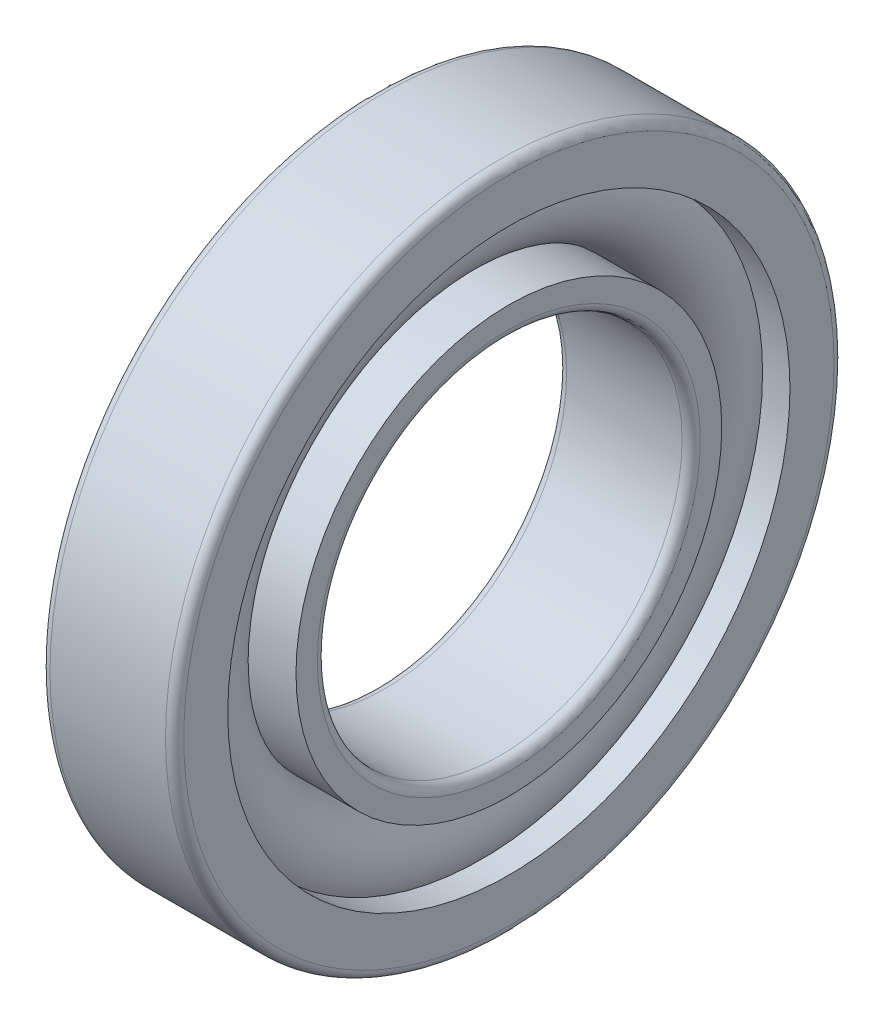
SolidWorks part; units mm, degrees
ref_plane "Plane1" through (0, 0, 0) normal (0, 0, 1) x (1, 0, 0)
ref_plane "Plane2" through (0, 0, 0) normal (0, 1, 0) x (1, 0, 0)
ref_plane "Plane3" through (0, 0, 0) normal (1, 0, 0) x (0, 0, -1)
sketch "Clipboard" plane through (0, 0, 0) normal (0, 0, 1) x (1, 0, 0)
  line L0 (-10, 0) -> (10, 0) construction
  line L1 (0, 0) -> (22.3471, -0.7804)
  line L2 (0, 0) -> (42.4741, 1.4832)
  line L3 (0, 0) -> (22.3471, -0.7804)
  line L4 (0, 0) -> (-22.3573, -0.3902)
  dimension "BallCLRad" = 42.5
sketch "CagSpiSke" plane through (0, 0, 0) normal (0, 0, 1) x (1, 0, 0)
  line L0 (1.875, 41.25) -> (1.875, 43.75)
  line L1 (1.875, 43.75) -> (-1.875, 43.75)
  line L2 (-1.875, 43.75) -> (-1.875, 41.25)
  line L3 (-1.875, 41.25) -> (1.875, 41.25)
  line L4 (-20.6375, 0) -> (20.6375, 0) construction
  line L5 (0, 0) -> (0, 23.7692) construction
  dimension "OD" = 87.5
  dimension "ID" = 82.5
revolve "CageSpine" add sketch "CagSpiSke" angle 0.001 about L4
ref_axis "Axis1" through (-50, 0, 0) along (1, 0, 0)
sketch "CagBalSke" plane through (0, 0, 0) normal (0, 0, 1) x (1, 0, 0)
  line L0 (-8.25, 42.5) -> (8.25, 42.5)
  line L1 (-1.905, 42.5) -> (1.905, 42.5) construction
  line L2 (-10, 0) -> (10, 0) construction
  line L3 (0, 0) -> (0, 24) construction
  arc A0 (8.25, 42.5) -> (-8.25, 42.5) centre (0, 42.5) cw
  dimension "BallCLRad" = 42.5
revolve "CageBall" [suppressed] add sketch "CagBalSke" angle 360 about L1 reverse direction yes
pattern_circular "CageBalls" [suppressed] count 2 every 180 about axis through (-50, 0, 0) along (1, 0, 0)
sketch "CagTrmODSke" plane through (0, 0, 0) normal (0, 0, 1) x (1, 0, 0)
  line L0 (8.251, 43.75) -> (8.251, 50.751)
  line L1 (8.251, 50.751) -> (-8.251, 50.751)
  line L2 (-8.251, 50.751) -> (-8.251, 43.75)
  line L3 (-8.251, 43.75) -> (8.251, 43.75)
  line L4 (-20.6375, 0) -> (20.6375, 0) construction
  line L5 (0, 0) -> (0, 25) construction
  dimension "Width" = 16.502
  dimension "ID" = 87.5
  dimension "OD" = 101.502
revolve "CageTrimOD" [suppressed] cut sketch "CagTrmODSke" angle 360 about L4 reverse direction yes
sketch "CagTrmIDSke" plane through (0, 0, 0) normal (0, 0, 1) x (1, 0, 0)
  line L0 (8.251, 34.251) -> (8.251, 41.25)
  line L1 (8.251, 41.25) -> (-8.251, 41.25)
  line L2 (-8.251, 41.25) -> (-8.251, 34.251)
  line L3 (-8.251, 34.251) -> (8.251, 34.251)
  line L4 (-20.6375, 0) -> (20.6375, 0) construction
  line L5 (0, 0) -> (0, 25) construction
  dimension "Width" = 16.502
  dimension "ID" = 68.502
  dimension "OD" = 82.5
revolve "CageTrimID" [suppressed] cut sketch "CagTrmIDSke" angle 360 about L4 reverse direction yes
sketch "BalSimSke" plane through (0, 0, 0) normal (0, 0, 1) x (1, 0, 0)
  line L0 (-10, 0) -> (10, 0) construction
  line L1 (-10, 42.5) -> (10, 42.5) construction
  line L2 (0, 0) -> (0, 23) construction
  circle A0 centre (0, 42.5) radius 7.5
  dimension "BallCLRad" = 42.5
  dimension "Ball_diameter" = 15
revolve "BallsSimplified" add sketch "BalSimSke" angle 360 about L0
sketch "BalDetSke" plane through (0, 0, 0) normal (0, 0, 1) x (1, 0, 0)
  line L0 (-7.5, 42.5) -> (7.5, 42.5)
  line L1 (-1.905, 42.5) -> (1.905, 42.5) construction
  line L2 (0, 0) -> (0, 25) construction
  arc A0 (7.5, 42.5) -> (-7.5, 42.5) centre (0, 42.5) cw
  dimension "BallCLRad" = 42.5
  dimension "Ball_diameter" = 15
revolve "BallDetailed" [suppressed] add sketch "BalDetSke" angle 360 about L1 reverse direction yes
sketch "InnRacSke" plane through (0, 0, 0) normal (0, 0, 1) x (1, 0, 0)
  line L0 (-6.4663, 38.75) -> (-11, 38.75)
  line L1 (-11, 38.75) -> (-11, 31.5)
  line L2 (-9.5, 30) -> (9.5, 30)
  line L3 (11, 31.5) -> (11, 35.025)
  line L4 (0, 35.025) -> (11, 35.025)
  line L5 (-20.6375, 0) -> (20.6375, 0) construction
  line L6 (0, 0) -> (0, 30) construction
  arc A0 (-11, 31.5) -> (-9.5, 30) centre (-9.5, 31.5) ccw
  arc A1 (9.5, 30) -> (11, 31.5) centre (9.5, 31.5) ccw
  arc A2 (0, 35.025) -> (-6.4663, 38.75) centre (0, 42.5) cw
  dimension "BallCLRad" = 42.5
  dimension "Fillet_radius" = 1.5
  dimension "Ball_diameter" = 14.95
  dimension "ID" = 60
  dimension "OD" = 77.5
  dimension "Width" = 22
revolve "InnerRace" add sketch "InnRacSke" angle 360 about L5 reverse direction yes
sketch "OutRacSke" plane through (0, 0, 0) normal (0, 0, 1) x (1, 0, 0)
  line L0 (0, 49.975) -> (-11, 49.975)
  line L1 (-11, 49.975) -> (-11, 53.5)
  line L2 (-9.5, 55) -> (9.5, 55)
  line L3 (11, 53.5) -> (11, 46.25)
  line L4 (11, 46.25) -> (6.4663, 46.25)
  line L5 (-20.6375, 0) -> (20.6375, 0) construction
  line L6 (0, 0) -> (0, 30) construction
  arc A0 (-11, 53.5) -> (-9.5, 55) centre (-9.5, 53.5) cw
  arc A1 (9.5, 55) -> (11, 53.5) centre (9.5, 53.5) cw
  arc A2 (6.4663, 46.25) -> (0, 49.975) centre (0, 42.5) ccw
  dimension "BallCLRad" = 42.5
  dimension "Fillet_radius" = 1.5
  dimension "Ball_diameter" = 14.95
  dimension "Width" = 22
revolve "OuterRace" add sketch "OutRacSke" angle 360 about L5 reverse direction yes
pattern_circular "BallsDetailed" [suppressed] count 2 every 180 about axis through (-50, 0, 0) along (1, 0, 0)
equation "\"BallCLRad@Clipboard\" = ( \"OD@OutRacSke\" + \"ID@InnRacSke\" ) / 4"
equation "\"BallCLRad@BalSimSke\" = \"BallCLRad@Clipboard\""
equation "\"BallCLRad@BalDetSke\" = \"BallCLRad@Clipboard\""
equation "\"BallCLRad@InnRacSke\" = \"BallCLRad@Clipboard\""
equation "\"BallCLRad@OutRacSke\" = \"BallCLRad@Clipboard\""
equation "\"Ball_diameter@InnRacSke\" = \"Ball_diameter@BalDetSke\" - 0.05"
equation "\"Ball_diameter@OutRacSke\" = \"Ball_diameter@BalDetSke\" - 0.05"
equation "\"Ball_diameter@BalSimSke\" = \"Ball_diameter@BalDetSke\""
equation "\"Width@OutRacSke\" = \"Width@InnRacSke\""
equation "\"Fillet_radius@OutRacSke\" = \"Fillet_radius@InnRacSke\""
equation "\"Max_count@Clipboard\" = int( 3.14159265 / atn(( \"Ball_diameter@BalDetSke\" / 2) / sqr( \"BallCLRad@Clipboard\"  *  \"BallCLRad@Clipboard\" - ( \"Ball_diameter@BalDetSke\" / 2) *  ( \"Ball_diameter@BalDetSke\" / 2))))"
equation "\"Max_count@Clipboard\" = ((sgn( \"Max_count@Clipboard\" - \"Count@Clipboard\" )-1)*( \"Max_count@Clipboard\" - \"Count@Clipboard\" ))/-2+ \"Count@Clipboard\""
equation "\"Count@BallsDetailed\" = int( \"Show_count@Clipboard\" ) "
equation "\"Count@BallsDetailed\" = ((sgn( \"Count@BallsDetailed\" - \"Max_count@Clipboard\" )-1)*( \"Count@BallsDetailed\" - \"Max_count@Clipboard\" ))/-2+ \"Max_count@Clipboard\""
equation "\"Count@BallsDetailed\" = ((sgn( \"Count@BallsDetailed\" - \"Min_count@Clipboard\" )+1)*( \"Count@BallsDetailed\" - \"Min_count@Clipboard\"))/2 +\"Min_count@Clipboard\""
equation "\"Angle@BallsDetailed\" = 360.0 / \"Max_count@Clipboard\""
equation "\"BallCLRad@CagBalSke\" = \"BallCLRad@Clipboard\""
equation "\"Count@CageBalls\" = \"Count@BallsDetailed\""
equation "\"Angle@CageBalls\" = \"Angle@BallsDetailed\""
equation "\"Angle@CageSpine\" =  \"Angle@CageBalls\" * ( \"Count@CageBalls\" -1 + int( \"Count@CageBalls\" / \"Max_count@Clipboard\" ) )  + 0.001 -  int( \"Count@CageBalls\" / \"Max_count@Clipboard\" ) * 0.001"
equation "\"Angle@CageSpine\" =  \"Angle@CageSpine\" * int( \"Min_count@Clipboard\" / 2) + int(1 / \"Min_count@Clipboard\")  * 0.001"
equation "\"CageWallOD@CagBalSke\" =  \"Ball_diameter@BalDetSke\" * 1.1"
equation "\"Thickness@CagSpiSke\" =  \"Ball_diameter@BalDetSke\" * 0.25"
equation "\"OD@CagTrmODSke\" = \"BallCLRad@Clipboard\" * 2 + \"CageWallOD@CagBalSke\" + 0.002"
equation "\"ID@CagTrmODSke\" = \"BallCLRad@Clipboard\" * 2 + \"Ball_diameter@BalDetSke\" / 6"
equation "\"OD@CagTrmIDSke\" = \"BallCLRad@Clipboard\" * 2 - \"Ball_diameter@BalDetSke\" / 6"
equation "\"ID@CagTrmIDSke\" = \"BallCLRad@Clipboard\" * 2 - \"CageWallOD@CagBalSke\" + 0.002"
equation "\"OD@CagSpiSke\" = \"ID@CagTrmODSke\""
equation "\"ID@CagSpiSke\" = \"OD@CagTrmIDSke\""
equation "\"Width@CagTrmODSke\" = \"CageWallOD@CagBalSke\" + 0.002"
equation "\"Width@CagTrmIDSke\" = \"CageWallOD@CagBalSke\" + 0.002"
